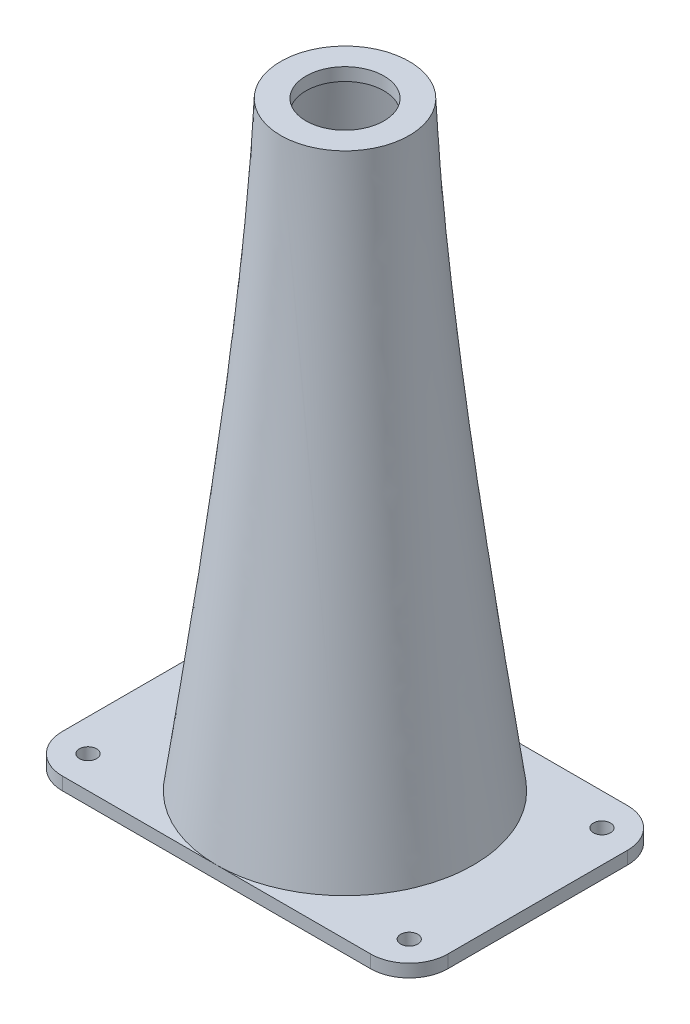
SolidWorks part; units mm, degrees
ref_plane "Front Plane" through (0, 0, 0) normal (0, 0, 1) x (1, 0, 0)
ref_plane "Top Plane" through (0, 0, 0) normal (0, 1, 0) x (1, 0, 0)
ref_plane "Right Plane" through (0, 0, 0) normal (1, 0, 0) x (0, 0, -1)
sketch "Sketch3" plane through (0, 0, 0) normal (0, 1, 0) x (1, 0, 0)
  circle A0 centre (0, 0) radius 30
  dimension "D1" = 60
ref_plane "Plane1" through (0, 140, 0) normal (0, 1, 0) x (1, 0, 0)
sketch "Sketch4" plane through (0, 140, 0) normal (0, 1, 0) x (1, 0, 0)
  circle A0 centre (0, 0) radius 15
  dimension "D1" = 30
loft "Loft2" add profiles "Sketch4", "Sketch3" connector at (10.7522, 140, 10.459) connector at (29.9923, 0, -0.6785)
sketch "Sketch43" plane through (0, 0, 0) normal (0, -1, 0) x (1, 0, 0)
  circle A1 centre (0, 0) radius 27.5
  dimension "D1" = 55
extrude "Cut-Extrude4" cut sketch "Sketch43" against normal blind 140 draft 6 contours A1
sketch "Sketch44" plane through (0, 140, 0) normal (0, 1, 0) x (1, 0, 0)
  circle A0 centre (0, 0) radius 9.1
  circle A1 centre (0, 0) radius 15 construction
  circle A2 centre (0, 0) radius 15
  dimension "D1" = 18.2
extrude "Boss-Extrude1" add sketch "Sketch44" against normal blind 3
sketch "Sketch45" plane through (0, 0, 0) normal (0, -1, 0) x (1, 0, 0)
  line L0 (0, 0) -> (0, 30) construction
  line L1 (-45, -30) -> (45, -30)
  line L2 (-45, -30) -> (-45, 30)
  line L3 (-45, 30) -> (45, 30)
  line L4 (45, -30) -> (45, 30)
  line L5 (-45, -30) -> (45, 30) construction
  line L6 (-45, 30) -> (45, -30) construction
  line L7 (0, 0) -> (45, 0) construction
  circle A0 centre (0, 0) radius 30 construction
  circle A1 centre (37.5, 22.5) radius 2
  circle A2 centre (37.5, -22.5) radius 2
  circle A3 centre (-37.5, -22.5) radius 2
  circle A4 centre (-37.5, 22.5) radius 2
  circle A5 centre (37.5, 22.5) radius 7.5
  point P0 (0, 0)
  circle M8 centre (0, 0) radius 27.5
  dimension "D2" = 4
  dimension "D3" = 15
  dimension "D1" = 90
extrude "Boss-Extrude2" add sketch "Sketch45" along normal blind 3 contours M8 | A5 L3 L1 L4 A2 | L3 L2 L1 A3 A4 | A5 A1 | A5 L4 L3 region at (-43.9183, 0, 0) region at (43.3247, 0, 28.3247) region at (32.3467, 0, 17.3467)
fillet "Fillet1" radius 9 4 edges at (45, -1.5, 30) (45, -1.5, -30) (-45, -1.5, -30) (-45, -1.5, 30)
